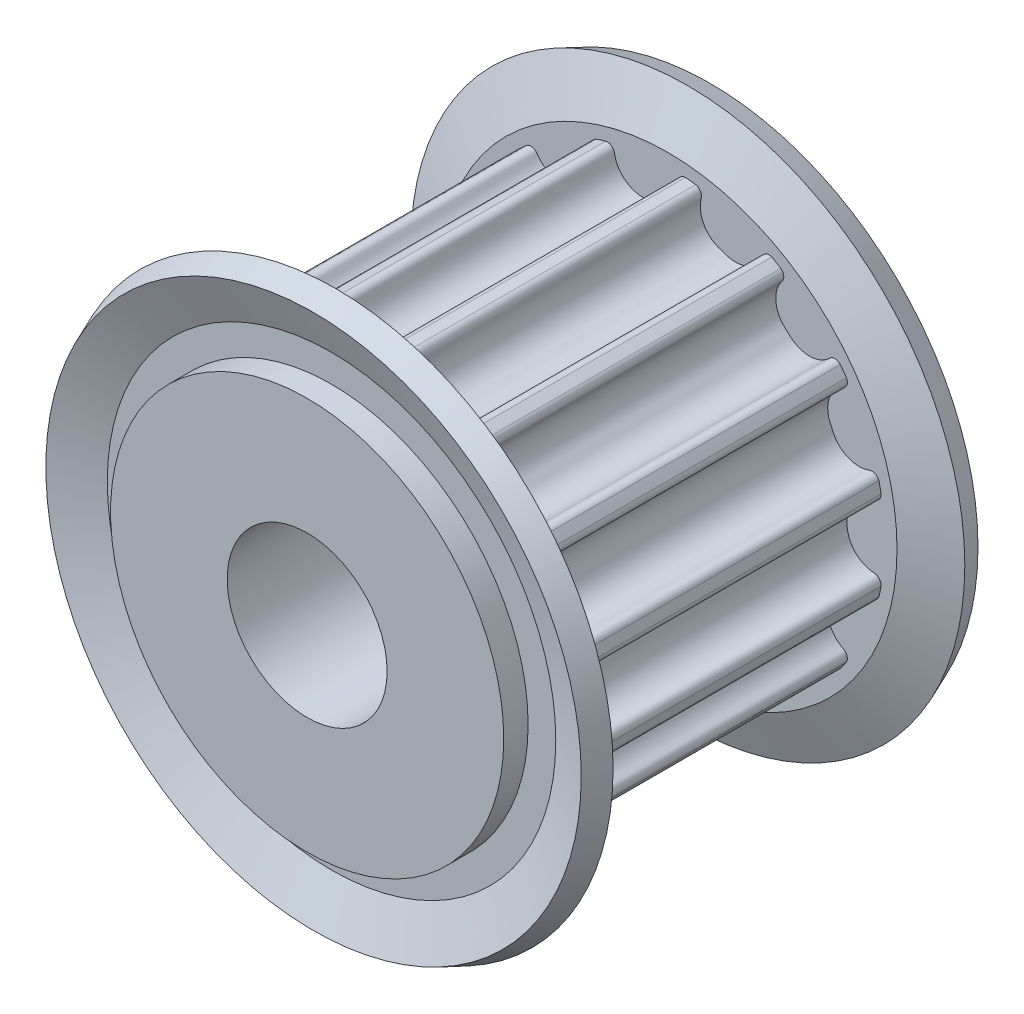
SolidWorks part; units mm, degrees
ref_plane "前视基准面" through (0, 0, 0) normal (0, 0, 1) x (1, 0, 0)
ref_plane "上视基准面" through (0, 0, 0) normal (0, 1, 0) x (1, 0, 0)
ref_plane "右视基准面" through (0, 0, 0) normal (1, 0, 0) x (0, 0, -1)
ref_axis "基准轴1" through (0, 0, 55) along (0, 0, -1)
sketch "SketchRevolveGearBelt01" plane through (0, 0, 0) normal (1, 0, 0) x (0, 0, -1)
  line L0 (0, 0) -> (1, 0) construction
  line L1 (6.4008, 0) -> (6.4008, 6.1455)
  line L2 (6.4008, 6.1455) -> (5.6388, 6.1455)
  line L3 (5.6388, 6.1455) -> (5.6388, 7.0099)
  line L4 (5.6388, 7.0099) -> (6.2015, 8.3685)
  line L5 (6.2015, 8.3685) -> (5.4975, 8.6601)
  line L6 (5.4975, 8.6601) -> (4.8768, 7.1615)
  line L7 (4.8768, 7.1615) -> (4.8768, 6.7805)
  line L8 (4.8768, 6.7805) -> (-4.8768, 6.7805)
  line L9 (-4.8768, 6.7805) -> (-4.8768, 7.1615)
  line L10 (-4.8768, 7.1615) -> (-5.4975, 8.6601)
  line L11 (-5.4975, 8.6601) -> (-6.2015, 8.3685)
  line L12 (-6.2015, 8.3685) -> (-5.6388, 7.0099)
  line L13 (-5.6388, 7.0099) -> (-5.6388, 6.1455)
  line L14 (-5.6388, 6.1455) -> (-6.4008, 6.1455)
  line L15 (-6.4008, 6.1455) -> (-6.4008, 0)
  line L16 (-6.4008, 0) -> (6.4008, 0)
  dimension "GearBeltFlange1OutsideLength" = 0.8644
  dimension "GearBeltFlange1X" = 0.5627
  dimension "GearBeltFlange1Y" = 1.3586
  dimension "GearBeltFlangeThickness" = 0.762
  dimension "GearBeltFlangeInside" = 0.381
  dimension "GearBeltOutsideDiameter" = 6.7805
  dimension "GearBeltFlange2X" = 0.5627
revolve "GearBelt01" add sketch "SketchRevolveGearBelt01" angle 360 about L0
sketch "SketchToothGearBelt01" plane through (0, 0, 0) normal (0, 0, 1) x (1, 0, 0)
  arc A0 (6.6611, 1.2728) -> (6.6611, -1.2728) centre (0, 0) cw
  spline S0 degree 3 poles (6.6611, -1.2728) (6.6636, -1.2597) (6.6656, -1.2396) (6.6648, -1.2127) (6.6624, -1.1927) (6.6583, -1.173) (6.6525, -1.1538) (6.645, -1.1351) (6.6358, -1.1171) (6.6252, -1.1) (6.6131, -1.084) (6.5996, -1.069) (6.5848, -1.0553) (6.569, -1.0429) (6.552, -1.032) (6.5342, -1.0226) (6.5157, -1.0148) (6.4965, -1.0087) (6.4769, -1.0041) (6.4278, -0.9983) (6.3619, -0.9935) (6.281, -0.9768) (6.2139, -0.9578) (6.1485, -0.9335) (6.0852, -0.9041) (6.0244, -0.8699) (5.9665, -0.8311) (5.9117, -0.7878) (5.8606, -0.7404) (5.8133, -0.6891) (5.7702, -0.6343) (5.7315, -0.5762) (5.6975, -0.5154) (5.6683, -0.452) (5.6442, -0.3865) (5.6253, -0.3194) (5.6117, -0.251) (5.6034, -0.1817) (5.6014, -0.1166) (5.6018, -0.056) (5.6017, 0) (5.6018, 0.056) (5.6014, 0.1166) (5.6034, 0.1817) (5.6117, 0.251) (5.6253, 0.3194) (5.6442, 0.3865) (5.6683, 0.452) (5.6975, 0.5154) (5.7315, 0.5762) (5.7702, 0.6343) (5.8133, 0.6891) (5.8606, 0.7404) (5.9117, 0.7878) (5.9665, 0.8311) (6.0244, 0.8699) (6.0852, 0.9041) (6.1485, 0.9335) (6.2139, 0.9578) (6.281, 0.9768) (6.3619, 0.9935) (6.4278, 0.9983) (6.4769, 1.0041) (6.4965, 1.0087) (6.5157, 1.0148) (6.5342, 1.0226) (6.552, 1.032) (6.569, 1.0429) (6.5848, 1.0553) (6.5996, 1.069) (6.6131, 1.084) (6.6252, 1.1) (6.6358, 1.1171) (6.645, 1.1351) (6.6525, 1.1538) (6.6583, 1.173) (6.6624, 1.1927) (6.6648, 1.2127) (6.6656, 1.2396) (6.6636, 1.2597) (6.6611, 1.2728) knots 0 0 0 0 0.010832 0.016248 0.021665 0.027081 0.032497 0.037913 0.043329 0.048745 0.054162 0.059578 0.064994 0.07041 0.075826 0.081242 0.086659 0.092075 0.097491 0.102907 0.132017 0.150785 0.169553 0.18832 0.207088 0.225855 0.244623 0.263391 0.282158 0.300926 0.319694 0.338461 0.357229 0.375997 0.394764 0.413532 0.4323 0.451067 0.469835 0.484917 0.5 0.515083 0.530165 0.548933 0.5677 0.586468 0.605236 0.624003 0.642771 0.661539 0.680306 0.699074 0.717842 0.736609 0.755377 0.774145 0.792912 0.81168 0.830447 0.849215 0.867983 0.897093 0.902509 0.907925 0.913341 0.918758 0.924174 0.92959 0.935006 0.940422 0.945838 0.951255 0.956671 0.962087 0.967503 0.972919 0.978335 0.983752 0.989168 1 1 1 1
extrude "ToothExtrudeCutGearBelt01" cut sketch "SketchToothGearBelt01" against normal blind 4.8768 and the other way blind 4.8768
pattern_circular "PatternGearBelt01" count 15 every 24 about axis through (0, 0, 55) along (0, 0, -1) of "ToothExtrudeCutGearBelt01"
sketch "BoreRevolveSketch" plane through (0, 0, 0) normal (1, 0, 0) x (0, 0, -1)
  line L0 (0, 0) -> (1, 0) construction
  line L1 (-6.4008, 0) -> (6.4008, 0)
  line L2 (6.4008, 0) -> (6.4008, 2.5)
  line L3 (6.4008, 2.5) -> (-6.4008, 2.5)
  line L4 (-6.4008, 2.5) -> (-6.4008, 0)
  dimension "TaperSide1" = 2.5
  dimension "TaperSide2" = 2.5
revolve "BoreRevolveCut" cut sketch "BoreRevolveSketch" angle 360 about L0
sketch "AuxiliarySketchGearBelt01" plane through (0, 0, 0) normal (0, 0, 1) x (1, 0, 0)
  circle A0 centre (0, 0) radius 7.1615 construction
  dimension "PitchDiameter" = 14.3229
